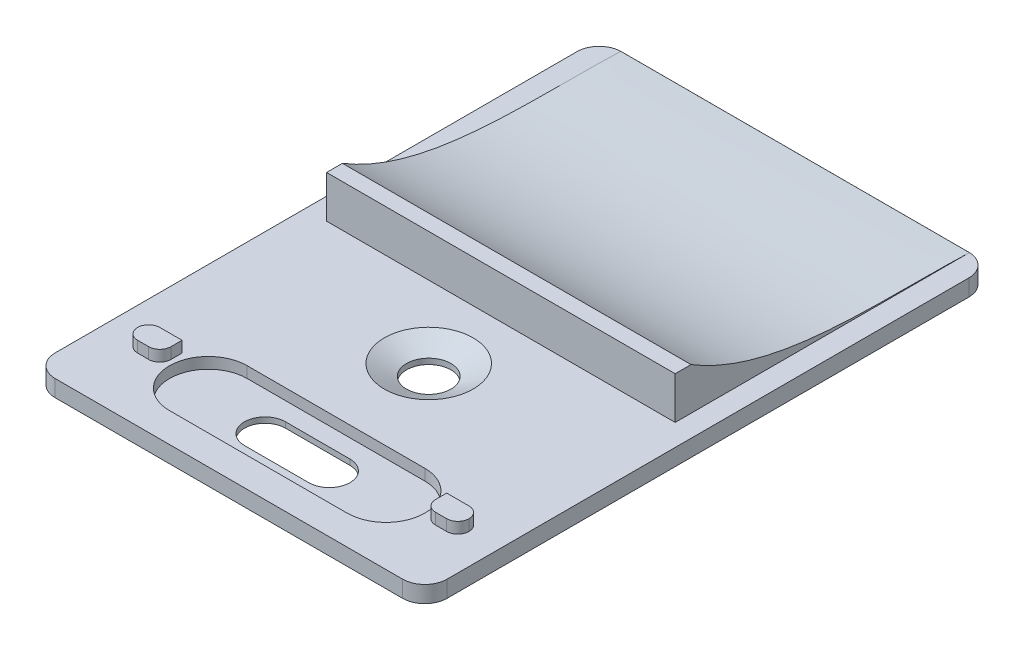
SolidWorks part; units mm, degrees
ref_plane "Front Plane" through (0, 0, 0) normal (0, 0, 1) x (1, 0, 0)
ref_plane "Top Plane" through (0, 0, 0) normal (0, 1, 0) x (1, 0, 0)
ref_plane "Right Plane" through (0, 0, 0) normal (1, 0, 0) x (0, 0, -1)
sketch "Sketch1" plane through (0, 0, 0) normal (0, 1, 0) x (1, 0, 0)
  line L1 (-17.65, 13) -> (17.65, 13)
  line L2 (-17.65, 13) -> (-17.65, -13)
  line L3 (-17.65, -13) -> (17.65, -13)
  line L4 (17.65, 13) -> (17.65, -13)
  line L5 (-17.65, 13) -> (17.65, -13) construction
  line L6 (-17.65, -13) -> (17.65, 13) construction
  point P0 (0, 0)
  dimension "D1" = 35.3
  dimension "D2" = 26
extrude "Boss-Extrude1" add sketch "Sketch1" along normal blind 1.5
sketch "Sketch2" plane through (0, 1.5, 0) normal (0, 1, 0) x (1, 0, 0)
  line L0 (17.65, 13) -> (-17.65, 13) construction
  line L1 (-15.9, 13) -> (15.9, 13)
  line L2 (-15.9, 13) -> (-15.9, 11.5)
  line L3 (-15.9, 11.5) -> (15.9, 11.5)
  line L4 (15.9, 13) -> (15.9, 11.5)
  point P6 (0, 11.5)
  dimension "D1" = 0
  dimension "D2" = 31.8
  dimension "D3" = 1.5
extrude "Boss-Extrude2" add sketch "Sketch2" along normal blind 3.8
sketch "Sketch3" plane through (0, 1.5, 0) normal (0, 1, 0) x (1, 0, 0)
  line L0 (-17.65, -13) -> (17.65, -13) construction
  circle A0 centre (0, 5) radius 2
  dimension "D1" = 18
  dimension "D2" = 4
extrude "Cut-Extrude1" cut sketch "Sketch3" against normal through all both and the other way through all
chamfer "Chamfer1" distance 2 distance2 1 1 edges at (0, 1.5, -3) first distance on face at (0, 1.5, -3)
fillet "Fillet1" radius 2 2 edges at (-17.65, 0.75, 13) (17.65, 0.75, 13)
sketch "Sketch4" plane through (0, 0, -13) normal (0, 0, -1) x (-1, 0, 0)
  line L0 (-15.9, 5.3) -> (-15.9, 1.5)
  line L1 (-15.9, 1.5) -> (-17.65, 1.5)
  line L2 (-17.65, 1.5) -> (-17.65, 0)
  line L3 (19.5981, 0) -> (-19.5981, 0) construction
  line L4 (-17.65, 1.5) -> (-17.65, 0) construction
  line L5 (-17.65, 0) -> (17.65, 0)
  line L6 (-17.65, 0) -> (17.65, 0) construction
  line L7 (17.65, 0) -> (17.65, 1.5)
  line L8 (17.65, 1.5) -> (15.9, 1.5)
  line L9 (15.9, 1.5) -> (15.9, 5.3)
  line L10 (15.9, 5.3) -> (-15.9, 5.3)
extrude "Boss-Extrude3" add sketch "Sketch4" along normal blind 25
fillet "Fillet2" radius 2 2 edges at (-17.65, 0.75, -38) (17.65, 0.75, -38)
fillet "Fillet3" [suppressed] radius 20
sketch "Sketch6" plane through (0, 1.5, 0) normal (0, 1, 0) x (1, 0, 0)
  line L7 (-17.65, 36) -> (-17.65, -11) construction
  line L8 (-14.92, -7.3) -> (-11.92, -7.3)
  line L9 (-14.92, -7.3) -> (-14.92, -5.3)
  line L10 (-14.92, -5.3) -> (-11.92, -5.3)
  line L11 (-11.92, -7.3) -> (-11.92, -5.3)
  line L12 (-15.65, -13) -> (15.65, -13) construction
  line L13 (0, -13) -> (0, -7.6395) construction
  line L14 (14.92, -5.3) -> (11.92, -5.3)
  line L15 (11.92, -7.3) -> (11.92, -5.3)
  line L16 (14.92, -7.3) -> (11.92, -7.3)
  line L17 (14.92, -7.3) -> (14.92, -5.3)
  dimension "D1" = 2.73
  dimension "D2" = 5.7
  dimension "D3" = 3
  dimension "D4" = 2
extrude "Boss-Extrude4" add sketch "Sketch6" along normal blind 1
fillet "Fillet4" radius 1 6 edges at (-14.92, 2, 5.3) (14.92, 2, 5.3) (14.92, 2, 7.3) (11.92, 2, 7.3) (-11.92, 2, 7.3) (-14.92, 2, 7.3)
sketch "Sketch7" plane through (0, 0, -11.5) normal (0, 0, 1) x (1, 0, 0)
  line L0 (-15.9, 1.5) -> (15.9, 1.5) construction
  line L1 (-15.7, 1.5) -> (-17.444, 1.5)
  line L2 (-15.7, 1.5) -> (-15.7, 7.8507)
  line L3 (-15.7, 7.8507) -> (-17.444, 7.8507)
  line L4 (-17.444, 1.5) -> (-17.444, 7.8507)
  line L5 (-15.9, 5.3) -> (-15.9, 1.5) construction
  line L6 (15.9, 5.3) -> (15.9, 1.5) construction
  line L7 (15.7, 1.5) -> (17.983, 1.5)
  line L8 (15.7, 1.5) -> (15.7, 9.1492)
  line L9 (15.7, 9.1492) -> (17.983, 9.1492)
  line L10 (17.983, 1.5) -> (17.983, 9.1492)
  dimension "D1" = 0.2
  dimension "D2" = 0.2
extrude "Cut-Extrude2" cut sketch "Sketch7" against normal through all
sketch "Sketch8" plane through (0, 1.5, 0) normal (0, 1, 0) x (1, 0, 0)
  line L0 (-7.5, -2.5) -> (7.5, -2.5) construction
  line L1 (-7.5, -0.9153) -> (7.5, -0.9153)
  line L2 (-7.5, -4.0847) -> (7.5, -4.0847)
  line L3 (-15.65, -13) -> (15.65, -13) construction
  arc A0 (-7.5, -0.9153) -> (-7.5, -4.0847) centre (-7.5, -2.5) ccw
  arc A1 (7.5, -4.0847) -> (7.5, -0.9153) centre (7.5, -2.5) ccw
  point P2 (0, -2.5)
  point P9 (0, -13)
  dimension "D1" = 0
  dimension "D2" = 10.5
  dimension "D3" = 15
extrude "Cut-Extrude3" [suppressed] cut sketch "Sketch8" against normal through all
sketch "Sketch9" [suppressed] plane through (0, 0, 0) normal (0, -1, 0) x (1, 0, 0)
  line L0 (-6.5847, 2.5) -> (6.5847, 2.5) construction
  line L1 (-6.5847, 6.5) -> (6.5847, 6.5)
  line L2 (-6.5847, -1.5) -> (6.5847, -1.5)
  arc A0 (-6.5847, 6.5) -> (-6.5847, -1.5) centre (-6.5847, 2.5) ccw
  arc A1 (6.5847, -1.5) -> (6.5847, 6.5) centre (6.5847, 2.5) ccw
  arc A2 (-7.5, 4.0847) -> (-7.5, 0.9153) centre (-7.5, 2.5) ccw construction
  arc A3 (7.5, 0.9153) -> (7.5, 4.0847) centre (7.5, 2.5) ccw construction
  point P2 (0, 2.5)
  point P7 (-10.5847, 2.5)
  point P11 (-9.0847, 2.5)
  point P12 (10.5847, 2.5)
  point P16 (9.0847, 2.5)
  dimension "D1" = 8
  dimension "D2" = 1.5
  dimension "D3" = 1.5
  dimension "D4" = 0
extrude "Cut-Extrude4" [suppressed] cut sketch "Sketch9" along normal offset from surface (0.8 mm away) 0.7 from surface up to face at (0, 0, -3) starting at face at (0, 1.5, -12.2964)
sketch "Sketch10" plane through (15.7, 0, 0) normal (1, 0, 0) x (0, 0, -1)
  line L0 (37.9994, 5.3) -> (11.5, 5.3) construction
  line L2 (12.9252, 5.3) -> (13.3546, 9.3095)
  line L3 (13.3546, 9.3095) -> (41.0747, 8.151)
  line L4 (41.0747, 8.151) -> (37.9994, 1.5)
  spline S0 degree 3 poles (12.9252, 5.3) (20.4054, 0.745) (29.7263, 1.7979) (37.9994, 1.5) knots 0 0 0 0 1 1 1 1
extrude "Cut-Extrude5" cut sketch "Sketch10" against normal through all both and the other way through all
sketch "Sketch12" plane through (0, 1.5, 0) normal (0, 1, 0) x (1, 0, 0)
  line L0 (-2.9, -6.85) -> (2.9, -6.85) construction
  line L1 (-2.9, -5) -> (2.9, -5)
  line L2 (-2.9, -8.7) -> (2.9, -8.7)
  line L3 (-15.65, -13) -> (15.65, -13) construction
  arc A0 (-2.9, -5) -> (-2.9, -8.7) centre (-2.9, -6.85) ccw
  arc A1 (2.9, -8.7) -> (2.9, -5) centre (2.9, -6.85) ccw
  point P2 (0, -6.85)
  point P9 (0, -13)
  point P10 (4.75, -6.85)
  point P11 (-4.75, -6.85)
  dimension "D1" = 4.3
  dimension "D2" = 8
  dimension "D3" = 0
  dimension "D4" = 9.5
extrude "Cut-Extrude6" cut sketch "Sketch12" against normal through all both
sketch "Sketch13" plane through (0, 0, 0) normal (0, -1, 0) x (1, 0, 0)
  line L0 (-8, 6.85) -> (8, 6.85) construction
  line L1 (-8, 10.35) -> (8, 10.35)
  line L2 (-8, 3.35) -> (8, 3.35)
  line L3 (2.9, 5) -> (-2.9, 5) construction
  arc A0 (-8, 10.35) -> (-8, 3.35) centre (-8, 6.85) ccw
  arc A1 (8, 3.35) -> (8, 10.35) centre (8, 6.85) ccw
  arc A2 (-2.9, 8.7) -> (-2.9, 5) centre (-2.9, 6.85) ccw construction
  point P2 (0, 6.85)
  point P7 (-11.5, 6.85)
  point P8 (11.5, 6.85)
  point P12 (-4.75, 6.85)
  point P15 (0, 5)
  dimension "D1" = 7
  dimension "D2" = 23
  dimension "D3" = 0
  dimension "D4" = 0
extrude "Cut-Extrude7" cut sketch "Sketch13" along normal offset from surface (1 mm away) 0.5 from surface up to face at (0, 0, 6.85) starting at face at (0, 1.5, 6.85)
